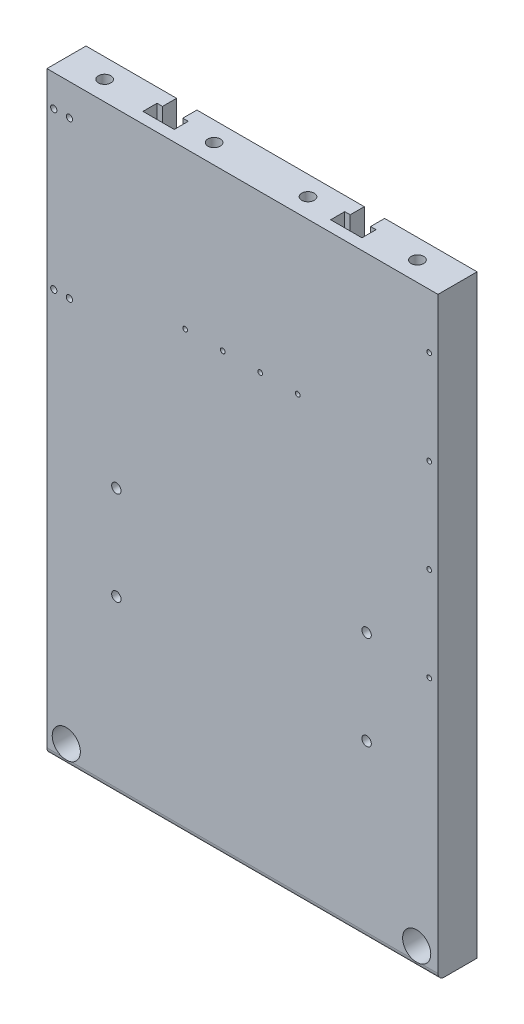
SolidWorks part; units mm, degrees
ref_plane "前视基准面" through (0, 0, 0) normal (0, 0, 1) x (1, 0, 0)
ref_plane "上视基准面" through (0, 0, 0) normal (0, 1, 0) x (1, 0, 0)
ref_plane "右视基准面" through (0, 0, 0) normal (1, 0, 0) x (0, 0, -1)
other "Configuration Table"
sketch "草图1" plane through (0, 0, 0) normal (0, 0, 1) x (1, 0, 0)
  line L0 (0.6138, 380.0763) -> (5, 380.0763)
  line L1 (0.6138, 0.0763) -> (250.6138, 0.0763)
  line L2 (0.6138, 0.0763) -> (0.6138, 380.0763)
  line L3 (0.6138, 380.0763) -> (250.6138, 380.0763)
  line L4 (250.6138, 0.0763) -> (250.6138, 380.0763)
  line L5 (5, 380.0763) -> (5, 360)
  circle A0 centre (13, 12.5) radius 9
  circle A1 centre (237, 12.5) radius 9
  circle A2 centre (5, 360) radius 2
  circle A3 centre (5, 260) radius 2
  circle A4 centre (15, 360) radius 2
  circle A5 centre (15, 260) radius 2
  circle A6 centre (89, 280) radius 1.5
  circle A7 centre (113, 280) radius 1.5
  circle A8 centre (137, 280) radius 1.5
  circle A9 centre (161, 280) radius 1.5
  circle A10 centre (45, 110) radius 3
  circle A11 centre (45, 170) radius 3
  circle A12 centre (205, 170) radius 3
  circle A13 centre (205, 110) radius 3
  circle A14 centre (245, 345) radius 1.5
  circle A15 centre (245, 285) radius 1.5
  circle A16 centre (245, 225) radius 1.5
  circle A17 centre (245, 165) radius 1.5
sketch "草图2" plane through (0, 0, 0) normal (0, 0, 1) x (1, 0, 0)
extrude "凸台-拉伸3" add sketch "草图1" along normal blind 25 contours A2 L0 L2 L1 L4 L3 A17 A16 A15 A14 A13 A12 A11 A10 A9 A8 A7 A6 A5 A4 A3 A1 A0 region at (125.6439, 190.9847, 0)
cosmetic thread "装饰螺纹线25" parameters "D2"=8
cosmetic thread "装饰螺纹线26" parameters "D2"=8
cosmetic thread "装饰螺纹线27" parameters "D2"=8
cosmetic thread "装饰螺纹线28" parameters "D2"=8
sketch "草图3" plane through (0, 380.0763, 0) normal (0, 1, 0) x (1, 0, 0)
  line L0 (71.5, 0) -> (71.5, -9)
  line L2 (58.5, 0) -> (58.5, -9)
  line L3 (71.5, -9) -> (75, -9)
  line L4 (55, -9) -> (58.5, -9)
  line L5 (55, -9) -> (55, -18)
  line L6 (75, -9) -> (75, -18)
  line L7 (55, -18) -> (75, -18)
  line L8 (178.5, 0) -> (178.5, -9)
  line L9 (191.5, 0) -> (191.5, -9)
  line L10 (191.5, -9) -> (195, -9)
  line L11 (178.5, -9) -> (175, -9)
  line L12 (175, -9) -> (175, -18)
  line L13 (175, -18) -> (195, -18)
  line L14 (195, -18) -> (195, -9)
  circle A1 centre (155, -12.5) radius 4
  circle A2 centre (95, -12.5) radius 4
  circle A3 centre (225, -12.5) radius 4
  circle A4 centre (25, -12.5) radius 4
  line M15 (250.6138, 0) -> (0.6138, 0)
extrude "切除-拉伸1" cut sketch "草图3" against normal blind 416 contours L5 L7 L6 L3 L0 L2 L4 M15 | L13 L14 L10 L9 L8 L11 L12 M15 region at (185, 380.0763, 9.9545) region at (65, 380.0763, 9.9545)
extrude "切除-拉伸2" cut sketch "草图3<4>" against normal blind 55 contours A2 | A1 | A3 | A4 region at (155, 380.0763, 12.5) region at (95, 380.0763, 12.5) region at (225, 380.0763, 12.5)
sketch "草图3<4>" plane through (0, 380.0763, 0) normal (0, 1, 0) x (1, 0, 0) same geometry as "草图3"
sketch "草图5" plane through (0, 0, 0) normal (0, 0, -1) x (-1, 0, 0)
  line L1 (-162.6237, 288.9406) -> (-86.2052, 288.9406)
  line L2 (-162.6237, 288.9406) -> (-162.6237, 270.7784)
  line L3 (-162.6237, 270.7784) -> (-86.2052, 270.7784)
  line L4 (-86.2052, 288.9406) -> (-86.2052, 270.7784)
extrude "凸台-拉伸4" add sketch "草图5" against normal blind 12
sketch "草图6" plane through (0, 0, 0) normal (0, 0, -1) x (-1, 0, 0)
  line L1 (-249.3176, 351.9945) -> (-239.3798, 351.9945)
  line L2 (-249.3176, 351.9945) -> (-249.3176, 154.2658)
  line L3 (-249.3176, 154.2658) -> (-239.3798, 154.2658)
  line L4 (-239.3798, 351.9945) -> (-239.3798, 154.2658)
extrude "凸台-拉伸5" add sketch "草图6" against normal blind 12
sketch "草图7" plane through (0, 0, 0) normal (0, 0, -1) x (-1, 0, 0)
  line L0 (-0.6138, 0.0763) -> (-0.6138, 380.0763) construction
  line L1 (-21.6747, 366.3184) -> (-0.6138, 366.3184)
  line L2 (-21.6747, 366.3184) -> (-21.6747, 254.5838)
  line L3 (-21.6747, 254.5838) -> (-0.6138, 254.5838)
  line L4 (-0.6138, 366.3184) -> (-0.6138, 254.5838)
extrude "凸台-拉伸6" add sketch "草图7" against normal blind 12
sketch "草图8" plane through (0, 0, 0) normal (0, 0, -1) x (-1, 0, 0)
  line L1 (-212.3129, 176.883) -> (-196.5494, 176.883)
  line L2 (-212.3129, 176.883) -> (-212.3129, 100.4644)
  line L3 (-212.3129, 100.4644) -> (-196.5494, 100.4644)
  line L4 (-196.5494, 176.883) -> (-196.5494, 100.4644)
extrude "凸台-拉伸7" add sketch "草图8" against normal blind 5
sketch "草图9" plane through (0, 0, 0) normal (0, 0, -1) x (-1, 0, 0)
  line L1 (-50.9087, 177.2256) -> (-39.9428, 177.2256)
  line L2 (-50.9087, 177.2256) -> (-50.9087, 101.8352)
  line L3 (-50.9087, 101.8352) -> (-39.9428, 101.8352)
  line L4 (-39.9428, 177.2256) -> (-39.9428, 101.8352)
extrude "凸台-拉伸8" add sketch "草图9" against normal blind 5
sketch "草图10" plane through (0, 0, 0) normal (0, 0, -1) x (-1, 0, 0)
  line L0 (-125, 0.0763) -> (-125, 380.0763)
  line L1 (-247.5994, 28.6221) -> (-226.2946, 28.6221)
  line L2 (-247.5994, 28.6221) -> (-247.5994, 1.6251)
  line L3 (-247.5994, 1.6251) -> (-226.2946, 1.6251)
  line L4 (-226.2946, 28.6221) -> (-226.2946, 1.6251)
  line L5 (-71.5, 0.0763) -> (-178.5, 0.0763) construction
  line L6 (-71.5, 380.0763) -> (-178.5, 380.0763) construction
  line L7 (-2.4006, 28.6221) -> (-2.4006, 1.6251)
  line L8 (-2.4006, 1.6251) -> (-23.7054, 1.6251)
  line L9 (-23.7054, 28.6221) -> (-23.7054, 1.6251)
  line L10 (-2.4006, 28.6221) -> (-23.7054, 28.6221)
  circle A2 centre (-237, 12.5) radius 6
  circle A3 centre (-13, 12.5) radius 6
extrude "凸台-拉伸11" add sketch "草图10" against normal blind 11 contours A2 | L7 L10 L9 L8 A3 region at (236.947, 28.2782, 0) region at (2.7445, 15.1236, 0)
fillet "圆角1" radius 4 1 edges at (125.6138, 0.0763, 25)
